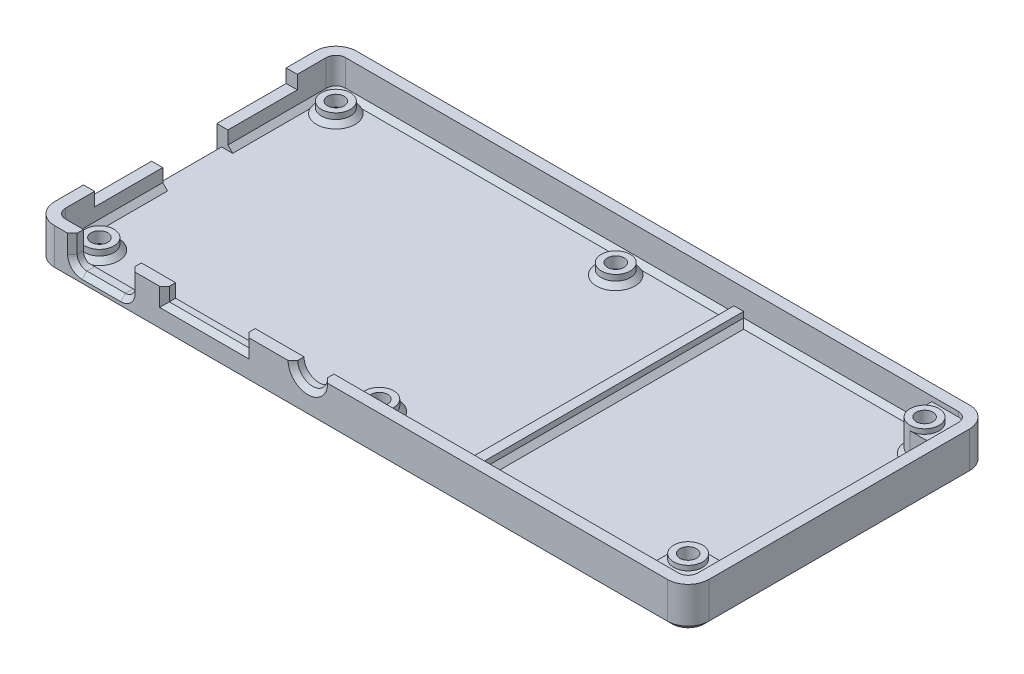
SolidWorks part; units mm, degrees
ref_plane "Front Plane" through (0, 0, 0) normal (0, 0, 1) x (1, 0, 0)
ref_plane "Top Plane" through (0, 0, 0) normal (0, 1, 0) x (1, 0, 0)
ref_plane "Right Plane" through (0, 0, 0) normal (1, 0, 0) x (0, 0, -1)
sketch "Sketch1" plane through (0, 0, 0) normal (0, 1, 0) x (1, 0, 0)
  line L0 (-71.5618, 3.106) -> (57.4382, 3.106) construction
  line L1 (-71.5618, 31.106) -> (57.4382, 31.106)
  line L2 (-71.5618, 31.106) -> (-71.5618, -24.894)
  line L3 (-71.5618, -24.894) -> (57.4382, -24.894)
  line L4 (57.4382, 31.106) -> (57.4382, -24.894)
  line L5 (-60.6618, -24.894) -> (-60.6618, -31.6828) construction
  line L6 (-68.0618, 27.606) -> (-10.0618, 27.606)
  line L7 (-68.0618, 27.606) -> (-68.0618, -21.394)
  line L8 (-68.0618, -21.394) -> (-10.0618, -21.394)
  line L9 (-10.0618, 27.606) -> (-10.0618, -21.394)
  line L10 (-39.5618, -24.894) -> (-39.5618, -31.6828) construction
  line L11 (-18.0618, -24.894) -> (-18.0618, -31.6828) construction
  line L12 (-65.4118, -26.5648) -> (-55.9118, -26.5648) construction
  line L13 (-48.0618, -26.5648) -> (-31.0618, -26.5648) construction
  line L14 (-22.0618, -26.5648) -> (-14.0618, -26.5648) construction
  line L15 (-72.5618, 9.606) -> (-72.5618, -3.394) construction
  line L16 (-71.5618, 3.106) -> (-72.5618, 3.106) construction
  dimension "D1" = 129
  dimension "D2" = 56
  dimension "D3" = 49
  dimension "D4" = 58
  dimension "D5" = 3.5
  dimension "D6" = 3.5
  dimension "D7" = 10.9
  dimension "D8" = 32
  dimension "D9" = 53.5
  dimension "D10" = 2
  dimension "D11" = 13
  dimension "D12" = 9.5
  dimension "D13" = 17
  dimension "D14" = 8
sketch "Sketch3" plane through (0, 0, 0) normal (0, 1, 0) x (1, 0, 0)
  line L4 (60.7382, 34.406) -> (-74.8618, 34.406)
  line L5 (-74.8618, 34.406) -> (-74.8618, -28.194)
  line L6 (-74.8618, -28.194) -> (60.7382, -28.194)
  line L7 (60.7382, -28.194) -> (60.7382, 34.406)
  line L8 (58.4382, 32.106) -> (-72.5618, 32.106)
  line L9 (58.4382, -25.894) -> (58.4382, 32.106)
  line L10 (-72.5618, -25.894) -> (58.4382, -25.894)
  line L11 (-72.5618, 32.106) -> (-72.5618, -25.894)
  line L12 (58.4382, 32.106) -> (-72.5618, 32.106)
  line L13 (58.4382, -25.894) -> (58.4382, 32.106)
  line L14 (-72.5618, -25.894) -> (58.4382, -25.894)
  line L15 (-72.5618, 32.106) -> (-72.5618, -25.894)
  line L16 (-7.0618, 3.106) -> (-7.0618, 34.406) construction
  line L17 (-71.5618, 3.106) -> (57.4382, 3.106) construction
  line L20 (-74.8618, 3.106) -> (52.7382, 3.106) construction
  line L25 (60.7382, -28.194) -> (60.7382, 34.406) construction
  line L26 (58.4382, -25.894) -> (58.4382, 32.106) construction
  dimension "D1" = 1
  dimension "D2" = 2.3
extrude "Boss-Extrude1" add sketch "Sketch3" along normal blind 8.5
sketch "Sketch5" plane through (0, 0, 0) normal (0, 1, 0) x (1, 0, 0)
  line L1 (-72.5618, 32.106) -> (58.4382, 32.106)
  line L2 (-72.5618, 32.106) -> (-72.5618, -25.894)
  line L3 (-72.5618, -25.894) -> (58.4382, -25.894)
  line L4 (58.4382, 32.106) -> (58.4382, -25.894)
extrude "Boss-Extrude2" add sketch "Sketch5" along normal blind 2
sketch "Sketch6" plane through (0, 2, 0) normal (0, 1, 0) x (1, 0, 0)
  circle A0 centre (-68.0618, 27.606) radius 3
  circle A1 centre (-68.0618, -21.394) radius 3
  circle A2 centre (-10.0618, -21.394) radius 3
  circle A3 centre (-10.0618, 27.606) radius 3
extrude "Boss-Extrude3" add sketch "Sketch6" along normal blind 2.2
sketch "Sketch10" plane through (0, 2, 0) normal (0, 1, 0) x (1, 0, 0)
  line L0 (58.4382, 32.106) -> (-72.5618, 32.106) construction
  line L1 (9.9382, 32.106) -> (11.9382, 32.106)
  line L2 (9.9382, 32.106) -> (9.9382, -25.894)
  line L3 (9.9382, -25.894) -> (11.9382, -25.894)
  line L4 (11.9382, 32.106) -> (11.9382, -25.894)
  line L5 (-72.5618, -25.894) -> (58.4382, -25.894) construction
  line L6 (-10.0618, 27.606) -> (-10.0618, -21.394) construction
  dimension "D1" = 2
  dimension "D2" = 20
extrude "Boss-Extrude4" add sketch "Sketch10" along normal blind 2.2
sketch "Sketch11" plane through (0, 0, 28.194) normal (0, 0, 1) x (1, 0, 0)
  line L0 (-74.8618, 8.5) -> (-74.8618, 0) construction
  line L1 (-66.8618, 8.5) -> (-54.8618, 8.5)
  line L2 (-66.8618, 8.5) -> (-66.8618, 2.7)
  line L3 (-66.8618, 2.7) -> (-54.8618, 2.7)
  line L4 (-54.8618, 8.5) -> (-54.8618, 2.7)
  line L5 (-74.8618, 0) -> (60.7382, 0) construction
  line L6 (-60.8618, 8.5) -> (-60.6618, 0) construction
  line L7 (-65.4118, 0) -> (-55.9118, 0) construction
  line L9 (-47.778, 8.5) -> (-31.278, 8.5)
  line L10 (-47.778, 8.5) -> (-47.778, 5.7)
  line L11 (-47.778, 5.7) -> (-31.278, 5.7)
  line L12 (-31.278, 8.5) -> (-31.278, 5.7)
  line L13 (-68.0618, 0) -> (-10.0618, 0) construction
  line L14 (-39.5618, 0) -> (-39.528, 8.5) construction
  line L15 (-48.0618, 0) -> (-31.0618, 0) construction
  line L16 (-18.0618, 0) -> (-18.0618, 8.5) construction
  line L17 (-22.0618, 0) -> (-14.0618, 0) construction
  line L18 (-74.8618, 8.5) -> (60.7382, 8.5) construction
  circle A0 centre (-18.0618, 8.5) radius 3.1
  dimension "D5" = 6.2
  dimension "D1" = 2.7
  dimension "D2" = 12
  dimension "D3" = 5.7
  dimension "D4" = 16.5
  dimension "D6" = 8
  dimension "D7" = 5.8
  dimension "D8" = 2.8
extrude "Cut-Extrude1" cut sketch "Sketch11" against normal up to next
sketch "Sketch12" plane through (-74.8618, 0, 0) normal (-1, 0, 0) x (0, 0, 1)
  line L0 (-3.106, 0) -> (-3.106, 8.5) construction
  line L1 (-27.606, 0) -> (21.394, 0) construction
  line L2 (-34.406, 8.5) -> (28.194, 8.5) construction
  line L3 (-24.106, 5.7) -> (17.894, 5.7)
  line L4 (-9.7329, 5.7) -> (3.7671, 5.7)
  line L5 (-9.7329, 5.7) -> (-9.7329, 2)
  line L6 (-9.7329, 2) -> (3.7671, 2)
  line L7 (3.7671, 5.7) -> (3.7671, 2)
  line L8 (-24.106, 8.5) -> (17.894, 8.5)
  line L9 (-24.106, 8.5) -> (-24.106, 5.7)
  line L11 (17.894, 8.5) -> (17.894, 5.7)
  line L12 (-9.7329, 3.85) -> (3.7671, 3.85) construction
  point P17 (-3.106, 5.7)
  dimension "D1" = 13.5
  dimension "D2" = 2.8
  dimension "D3" = 3.7
  dimension "D4" = 6.5
extrude "Cut-Extrude2" cut sketch "Sketch12" against normal up to next contours L9 L3 L11 L8 | L7 L6 L5 L4
fillet "Fillet6" radius 2 1 edges at (58.4382, 5.25, -32.106)
fillet "Fillet8" radius 2 2 edges at (-72.5618, 5.25, 25.894) (-72.5618, 5.25, -32.106)
chamfer "Chamfer1" distance 1 angle 45 4 edges at (-68.0618, 2, 24.394) (-10.0618, 2, 24.394) (-10.0618, 2, -24.606) (-68.0618, 2, -24.606)
sketch "Sketch24" plane through (0, 2, 0) normal (0, 1, 0) x (1, 0, 0)
  line L0 (11.9382, 3.106) -> (61.5789, 3.106) construction
  line L1 (11.9382, -25.894) -> (11.9382, 32.106) construction
  line L2 (53.9382, -18.394) -> (58.4382, -18.394)
  line L3 (58.4382, -25.894) -> (58.4382, 30.106) construction
  line L4 (-68.0618, 27.606) -> (-10.0618, 27.606) construction
  line L5 (-68.0618, 27.606) -> (-68.0618, -21.394) construction
  line L6 (-68.0618, -21.394) -> (-10.0618, -21.394) construction
  line L7 (-10.0618, 27.606) -> (-10.0618, -21.394) construction
  line L8 (-10.0618, 27.606) -> (53.9382, 27.606) construction
  line L9 (-10.0618, 27.606) -> (-10.0618, -21.394) construction
  line L10 (-10.0618, -21.394) -> (53.9382, -21.394) construction
  line L11 (53.9382, 27.606) -> (53.9382, -21.394) construction
  line L12 (50.9382, -21.394) -> (50.9382, -25.894)
  line L13 (11.9382, -25.894) -> (58.4382, -25.894) construction
  line L14 (58.4382, -25.894) -> (58.4382, 30.106) construction
  line L15 (58.4382, -18.394) -> (58.4382, -25.894)
  line L16 (58.4382, -25.894) -> (50.9382, -25.894)
  line L17 (50.9382, 27.606) -> (50.9382, 32.106)
  line L18 (56.4382, 32.106) -> (-70.5618, 32.106) construction
  line L19 (53.9382, 24.606) -> (58.4382, 24.606)
  line L20 (58.4382, 24.606) -> (58.4382, 32.106)
  line L21 (58.4382, 32.106) -> (50.9382, 32.106)
  arc A0 (50.9382, -21.394) -> (53.9382, -18.394) centre (53.9382, -21.394) cw
  arc A1 (50.9382, 27.606) -> (53.9382, 24.606) centre (53.9382, 27.606) ccw
  dimension "D2" = 4.5
extrude "Boss-Extrude7" add sketch "Sketch24" along normal up to surface (6.5 mm away) up to face at (-8.3784, 8.5, -11.175)
fillet "Fillet20" radius 4.3 4 edges at (60.7382, 4.25, 28.194) (-74.8618, 4.25, -34.406) (-74.8618, 4.25, 28.194) (60.7382, 4.25, -34.406)
chamfer "Chamfer5" distance 1 angle 45 17 edges at (-72.5618, 2, 13.8305) (-72.5618, 2, -19.9195) (-71.976, 2, 25.3082) (-71.976, 2, -31.5202) (-30.3118, 2, 25.894) (-30.3118, 2, -32.106) (9.9382, 2, -3.106) (11.9382, 2, -3.106) (31.4382, 2, -32.106) (31.4382, 2, 25.894) (51.8169, 2, 19.2727) (58.4382, 2, -3.106) (51.8169, 2, -25.4847) (50.9382, 2, 23.644) (56.1882, 2, 18.394) (56.1882, 2, -24.606) (50.9382, 2, -29.856)
hole_wizard "CSK for #4 Flat Head Socket Cap Screw1" positions "Sketch28" profile "Sketch27" countersink size "#4" standard "ANSI Inch"
sketch "Sketch28" plane through (0, 0, 0) normal (0, -1, 0) x (-1, 0, 0)
  point P0 (68.0618, 27.606)
  point P4 (68.0618, -21.394)
  point P8 (-53.9382, 27.606)
  point P12 (-53.9382, -21.394)
  point P15 (10.0618, -21.394)
  point P19 (10.0618, 27.606)
sketch "Sketch27" plane through (-68.0618, 0, -27.606) normal (1, 0, 0) x (0, 0, -1)
  line L0 (0, 0) -> (0, 15.0378)
  line L1 (0, 15.0378) -> (1.7272, 14)
  line L2 (1.7272, 14) -> (1.7272, 1.8805)
  line L3 (1.7272, 1.8805) -> (3.3619, 0)
  line L5 (3.3619, 0) -> (0, 0)
  line L6 (-1.7272, 1.8805) -> (-3.3619, 0) construction
  line L10 (0, 15.0378) -> (-1.7272, 14) construction
  line L11 (0, -6.35) -> (0, 107.95) construction
  dimension "Hole Dia." = 3.4544
  dimension "Hole Depth" = 14
  dimension "Near C'Sink Dia." = 6.7238
  dimension "Near C'Sink Angle" = 82
  dimension "Drill Angle" = 118
chamfer "Chamfer7" distance 1 angle 45 8 edges at (-74.8618, 0, -3.106) (-73.6023, 0, 26.9346) (-73.6023, 0, -33.1466) (-7.0618, 0, 28.194) (-7.0618, 0, -34.406) (59.4788, 0, 26.9346) (59.4788, 0, -33.1466) (60.7382, 0, -3.106)
chamfer "Chamfer8" distance 1 angle 45 1 edges at (-74.8618, 2, -2.9829)
sketch "Sketch29" plane through (0, 8.5, 0) normal (0, 1, 0) x (1, 0, 0)
  line L0 (53.9382, 24.606) -> (58.4382, 24.606)
  line L1 (58.4382, 24.606) -> (58.4382, 30.106)
  line L2 (56.4382, 32.106) -> (50.9382, 32.106)
  line L3 (50.9382, 32.106) -> (50.9382, 27.606)
  line L4 (53.9382, -18.394) -> (58.4382, -18.394)
  line L5 (58.4382, -18.394) -> (58.4382, -23.894)
  line L6 (56.4382, -25.894) -> (50.9382, -25.894)
  line L7 (50.9382, -25.894) -> (50.9382, -21.394)
  arc A0 (53.9382, 24.606) -> (50.9382, 27.606) centre (53.9382, 27.606) ccw
  arc A1 (56.4382, 32.106) -> (58.4382, 30.106) centre (56.4382, 30.106) cw
  arc A2 (50.9382, -21.394) -> (53.9382, -18.394) centre (53.9382, -21.394) ccw
  arc A3 (56.4382, -25.894) -> (58.4382, -23.894) centre (56.4382, -23.894) ccw
extrude "Cut-Extrude3" cut sketch "Sketch29" against normal blind 1
fillet "Fillet21" radius 2 2 edges at (-54.8618, 2.7, 26.894) (-66.8618, 2.7, 26.894)
chamfer "Chamfer9" distance 1 angle 45 9 edges at (-18.0618, 5.4, 28.194) (-31.278, 7.1, 28.194) (-39.528, 5.7, 28.194) (-47.778, 7.1, 28.194) (-54.8618, 6.6, 28.194) (-55.4476, 3.2858, 28.194) (-60.8618, 2.7, 28.194) (-66.276, 3.2858, 28.194) (-66.8618, 6.6, 28.194)
